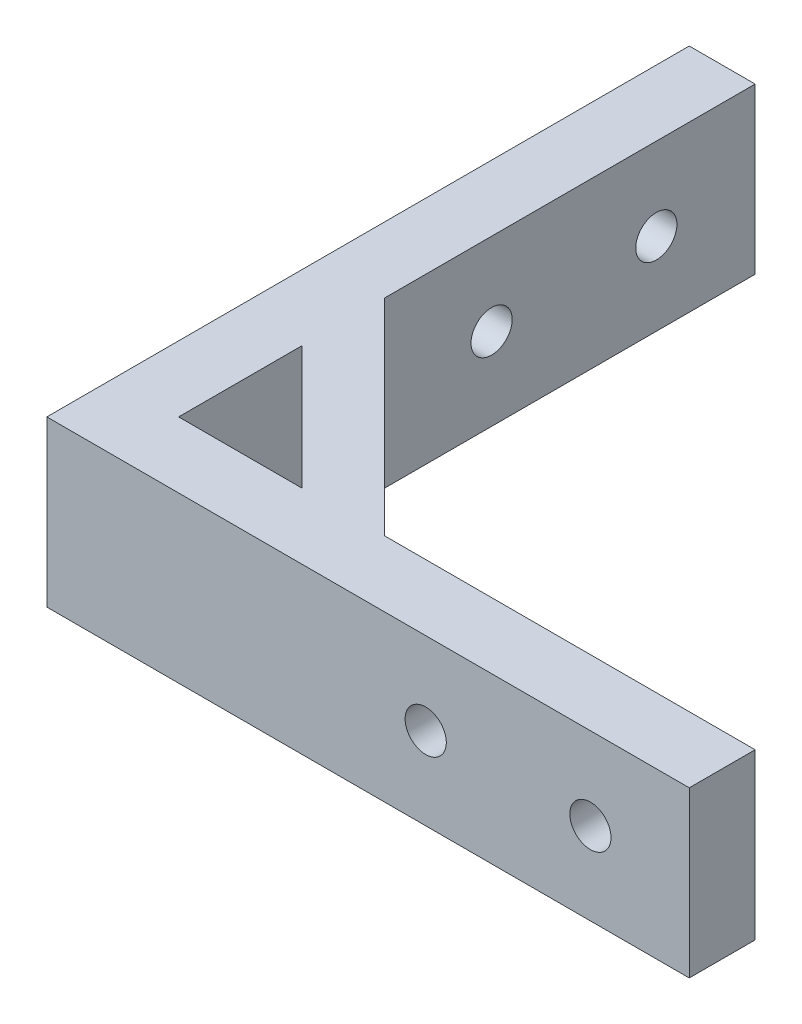
SolidWorks part; units mm, degrees
ref_plane "Front Plane" through (0, 0, 0) normal (0, 0, 1) x (1, 0, 0)
ref_plane "Top Plane" through (0, 0, 0) normal (0, 1, 0) x (1, 0, 0)
ref_plane "Right Plane" through (0, 0, 0) normal (1, 0, 0) x (0, 0, -1)
sketch "Sketch1" plane through (0, 0, 0) normal (0, 1, 0) x (1, 0, 0)
  line L0 (8, 23) -> (23, 8)
  line L1 (78, 78) -> (0, 78)
  line L2 (78, 78) -> (78, 0)
  line L3 (78, 0) -> (0, 0)
  line L4 (0, 78) -> (0, 0)
  line L5 (8, 33) -> (33, 8)
  line L7 (78, 78) -> (8, 78)
  line L8 (78, 78) -> (78, 8)
  line L9 (78, 8) -> (8, 8)
  line L10 (8, 78) -> (8, 8)
  point P0 (0, 0)
  point P12 (0, 0)
  dimension "D1" = 78
  dimension "D2" = 78
  dimension "D3" = 8
  dimension "D4" = 8
  dimension "D5" = 15
  dimension "D6" = 15
  dimension "D7" = 25
  dimension "D8" = 25
extrude "Boss-Extrude1" add sketch "Sketch1" along normal mid plane 20 contours L10 L1 L4 L3 L2 L9 region at (6.8969, 0, -15.5)
extrude "Boss-Extrude2" add sketch "Sketch1<3>" along normal mid plane 20 contours L5 L10 L0 L9 region at (18.2083, 0, -18.2083)
sketch "Sketch1<3>" plane through (0, 0, 0) normal (0, 1, 0) x (1, 0, 0) same geometry as "Sketch1"
sketch "Sketch2" plane through (8, 0, 0) normal (1, 0, 0) x (0, 0, -1)
  line L0 (78, 10) -> (78, -10) construction
  line L1 (78, 10) -> (33, 10) construction
  circle A0 centre (46, 0) radius 2.5
  circle A1 centre (66, 0) radius 2.5
  dimension "D1" = 5
  dimension "D2" = 12
  dimension "D3" = 20
  dimension "D4" = 10
  dimension "D5" = 10
sketch "Sketch3" plane through (0, 0, -8) normal (0, 0, -1) x (-1, 0, 0)
  line L0 (-78, 10) -> (-78, -10) construction
  line L1 (-78, -10) -> (-33, -10) construction
  circle A0 centre (-66, 0) radius 2.5
  circle A1 centre (-46, 0) radius 2.5
  point P8 (-46.4844, 0.3406)
  dimension "D1" = 5
  dimension "D2" = 12
  dimension "D3" = 20
  dimension "D4" = 10
  dimension "D5" = 10
extrude "Cut-Extrude1" cut sketch "Sketch2" against normal up to surface (8 mm away) up to face at (0, 0, -39)
extrude "Cut-Extrude2" cut sketch "Sketch3" against normal up to surface (8 mm away) up to face at (39, 0, 0)
